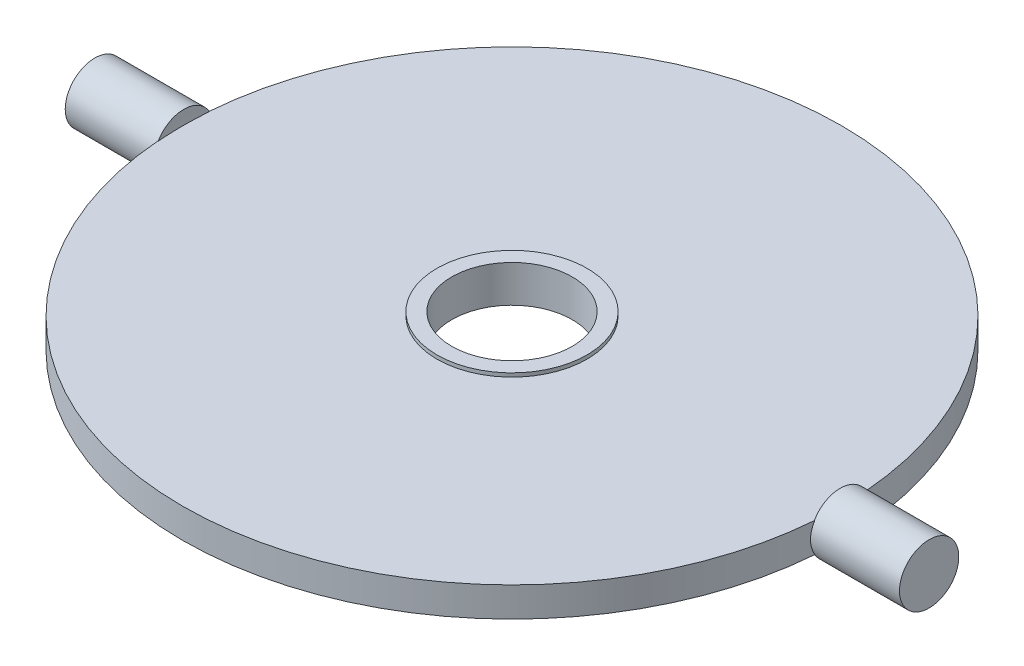
SolidWorks part; units mm, degrees
ref_plane "Front Plane" through (0, 0, 0) normal (0, 0, 1) x (1, 0, 0)
ref_plane "Top Plane" through (0, 0, 0) normal (0, 1, 0) x (1, 0, 0)
ref_plane "Right Plane" through (0, 0, 0) normal (1, 0, 0) x (0, 0, -1)
sketch "Sketch1" plane through (0, 0, 0) normal (0, 1, 0) x (1, 0, 0)
  line L0 (-76.4354, 0) -> (76.4354, 0) construction
  line L1 (-56.2697, 4) -> (-56.2697, -4)
  line L2 (0, 44.45) -> (0, -44.45) construction
  line L3 (-56.2697, 4) -> (-44.2697, 4)
  line L4 (-56.2697, -4) -> (-44.2697, -4)
  line L5 (56.2697, -4) -> (44.2697, -4)
  line L6 (56.2697, 4) -> (56.2697, -4)
  line L7 (56.2697, 4) -> (44.2697, 4)
  line L8 (-56.2697, 0) -> (-44.45, 0)
  line L9 (56.2697, 0) -> (44.45, 0)
  circle A0 centre (0, 0) radius 44.45
  circle A1 centre (0, 0) radius 8.125
  circle A2 centre (0, 0) radius 10.125
  point P6 (0, 0)
  point P9 (-56.2697, 0)
  dimension "D1" = 88.9
  dimension "D4" = 16.25
  dimension "D2" = 8
  dimension "D3" = 12
  dimension "D5" = 2
extrude "Boss-Extrude1" add sketch "Sketch1" along normal mid plane 4 contours A0 L1 region at (0, 0, -43.1928)
revolve "Revolve1" add sketch "Sketch1<6>" angle 360 about L0 region at (-50.3297, 0, 2.0051) region at (50.3297, 0, 2.0051)
sketch "Sketch1<6>" plane through (0, 0, 0) normal (0, 1, 0) x (1, 0, 0) same geometry as "Sketch1"
extrude "Boss-Extrude2" add sketch "Sketch1<7>" along normal mid plane 5 contours A2 A1 region at (-9.8386, 0, 0)
sketch "Sketch1<7>" plane through (0, 0, 0) normal (0, 1, 0) x (1, 0, 0) same geometry as "Sketch1"
